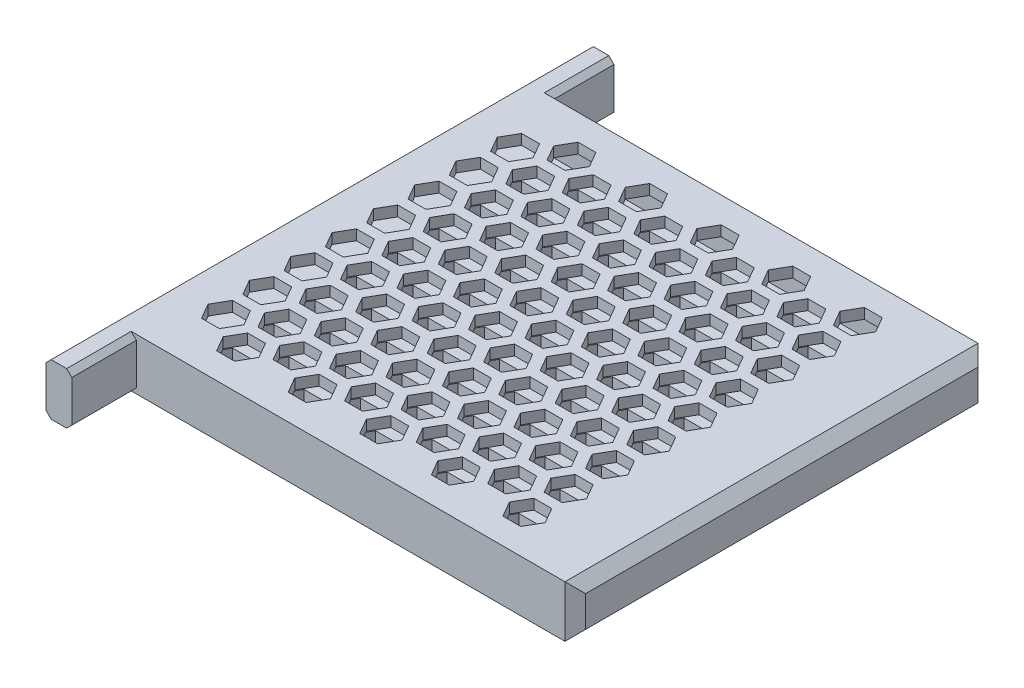
SolidWorks part; units mm, degrees
ref_plane "Plan de face" through (0, 0, 0) normal (0, 0, 1) x (1, 0, 0)
ref_plane "Plan de dessus" through (0, 0, 0) normal (0, 1, 0) x (1, 0, 0)
ref_plane "Plan de droite" through (0, 0, 0) normal (1, 0, 0) x (0, 0, -1)
sketch "Esquisse1" plane through (0, 0, 0) normal (0, 1, 0) x (1, 0, 0)
  line L1 (-45, 40) -> (45, 40)
  line L2 (-45, 40) -> (-45, -40)
  line L3 (-45, -40) -> (45, -40)
  line L4 (45, 40) -> (45, -40)
  line L5 (-45, 40) -> (45, -40) construction
  line L6 (-45, -40) -> (45, 40) construction
  point P0 (0, 0)
  dimension "D1" = 90
  dimension "D2" = 80
extrude "Boss.-Extru.1" add sketch "Esquisse1" along normal blind 10 contours L2 L1 L4 L3
chamfer "Chanfrein1" distance 2 angle 45 4 edges at (45, 5, -40) (45, 0, 0) (45, 5, 40) (45, 10, 0)
shell "Coque1" thickness 2 removed face at (-45, 5, 0)
sketch "Esquisse2" plane through (0, 10, 0) normal (0, 1, 0) x (1, 0, 0)
  line L0 (-45, 0) -> (-38.0858, 0)
  line L1 (-45, 40) -> (-40, 40)
  line L2 (-45, 40) -> (-45, 52.5)
  line L3 (-45, 52.5) -> (-40, 52.5)
  line L4 (-40, 40) -> (-40, 52.5)
  line L5 (-45, 40) -> (-45, -40) construction
  line L6 (-45, -52.5) -> (-40, -52.5)
  line L7 (-40, -40) -> (-40, -52.5)
  line L8 (-45, -40) -> (-40, -40)
  line L9 (-45, -40) -> (-45, -52.5)
  dimension "D1" = 105
  dimension "D2" = 5
extrude "Boss.-Extru.2" add sketch "Esquisse2" against normal up to surface (10 mm away) contours L6 L7 L8 L9 | L2 L1 L4 L3 up to face at (-1, 0, 0)
chamfer "Chanfrein2" distance 1 angle 45 6 edges at (-45, 10, 0) (-45, 0, 0) (-40, 10, 46.25) (-40, 0, 46.25) (-40, 10, -46.25) (-40, 0, -46.25)
sketch "Esquisse3" plane through (0, 0, 0) normal (0, -1, 0) x (1, 0, 0)
  line L0 (0, 0) -> (-2.5981, 1.5)
  line L1 (-40, 40) -> (43, 40)
  line L2 (-40, 40) -> (-40, -40)
  line L3 (-40, -40) -> (43, -40)
  line L4 (43, 40) -> (43, -40)
  line L268 (3.4641, 0) -> (1.7321, 3)
  line L269 (1.7321, 3) -> (-1.7321, 3)
  line L270 (-1.7321, 3) -> (-3.4641, 0)
  line L271 (-3.4641, 0) -> (-1.7321, -3)
  line L272 (-1.7321, -3) -> (1.7321, -3)
  line L273 (1.7321, -3) -> (3.4641, 0)
  line L429 (43, 0) -> (40.5422, 0) construction
  line L430 (-40, -38) -> (43, -38)
  line L558 (-40, 38) -> (43, 38)
  line L559 (-41, 40) -> (43, 40) construction
  circle A0 centre (0, 0) radius 3 construction
  dimension "D1" = 6
  dimension "D8" = 2
extrude "Enlèv. mat.-Extru.1" cut sketch "Esquisse3" along direction (0, -1, 0) on the side against the normal up to surface (10 mm away) contours L272 L273 L268 L269 L270 L271 region at (2.5187, 0, -1.4542) up to face at (-20.75, 10, 0)
pattern_linear "Répétition linéaire2" count 2 spacing 8 along (-0.866, 0, 0.5) of "Enlèv. mat.-Extru.1"
pattern_linear "Répétition linéaire3" count 4 spacing 8 along (0, 0, 1) count 5 spacing 8 along (0, 0, -1) of "Répétition linéaire2"
pattern_linear "Répétition linéaire4" count 2 spacing 32 along (0, 0, 1) of "Enlèv. mat.-Extru.1"
pattern_linear "Répétition linéaire5" count 3 spacing 13.86 along (1, 0, 0) count 3 spacing 13.86 along (-1, 0, 0) of "Répétition linéaire2", "Répétition linéaire3", "Répétition linéaire4" pattern seed only yes
